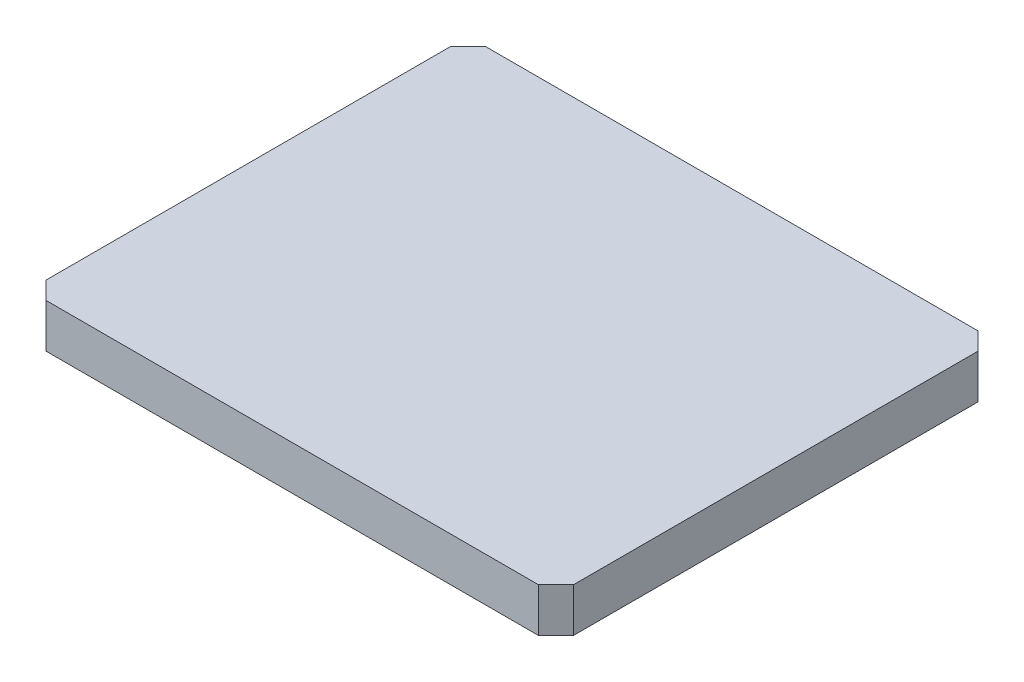
SolidWorks part; units mm, degrees
ref_plane "Front Plane" through (0, 0, 0) normal (0, 0, 1) x (1, 0, 0)
ref_plane "Top Plane" through (0, 0, 0) normal (0, 1, 0) x (1, 0, 0)
ref_plane "Right Plane" through (0, 0, 0) normal (1, 0, 0) x (0, 0, -1)
sketch "Sketch1" plane through (0, 0, 0) normal (0, 1, 0) x (1, 0, 0)
  line L1 (0, 0) -> (60, 0)
  line L2 (0, 0) -> (0, 50)
  line L3 (0, 50) -> (60, 50)
  line L4 (60, 0) -> (60, 50)
  dimension "D1" = 50
  dimension "D2" = 60
extrude "Boss-Extrude1" add sketch "Sketch1" along normal blind 5
chamfer "Chamfer1" distance 2 angle 45 4 edges at (60, 2.5, 0) (60, 2.5, -50) (0, 2.5, 0) (0, 2.5, -50)
